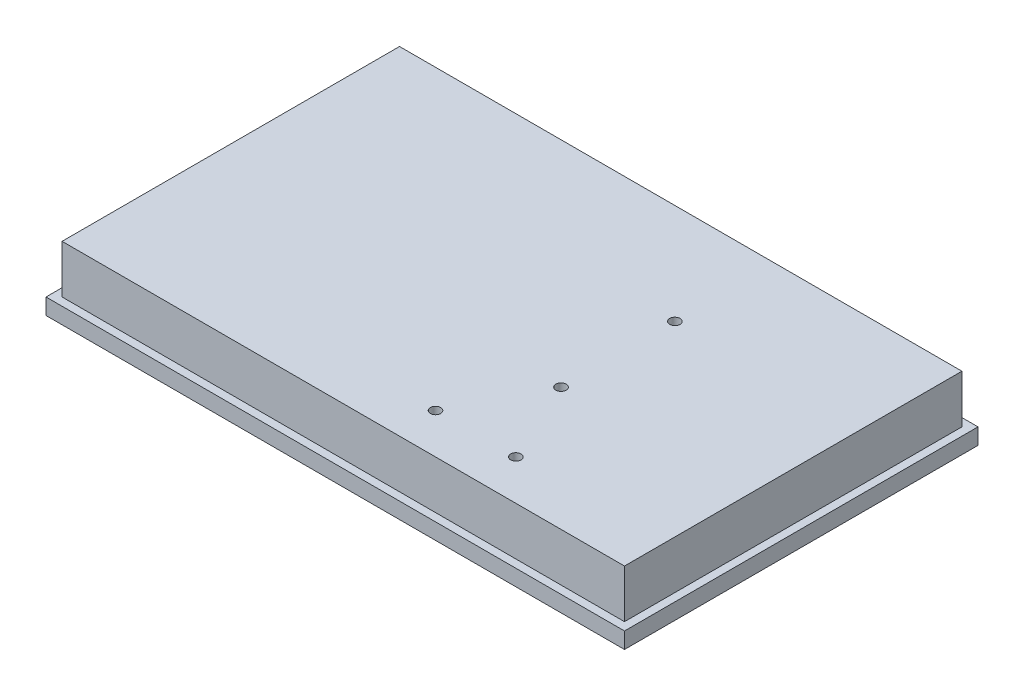
SolidWorks part; units mm, degrees
material "Gray Cast Iron"
ref_plane "Front Plane" through (0, 0, 0) normal (0, 0, 1) x (1, 0, 0)
ref_plane "Top Plane" through (0, 0, 0) normal (0, 1, 0) x (1, 0, 0)
ref_plane "Right Plane" through (0, 0, 0) normal (1, 0, 0) x (0, 0, -1)
sketch "Sketch1" plane through (0, 0, 0) normal (0, 1, 0) x (1, 0, 0)
  line L0 (-228.6, -139.7) -> (228.6, -139.7)
  line L1 (228.6, -139.7) -> (228.6, 139.7)
  line L2 (228.6, 139.7) -> (-228.6, 139.7)
  line L3 (-228.6, 139.7) -> (-228.6, -139.7)
  dimension "D1" = 457.2
  dimension "D2" = 279.4
  dimension "D3" = 228.6
  dimension "D4" = 139.7
extrude "Boss-Extrude1" add sketch "Sketch1" along normal blind 12.7
sketch "Sketch2" plane through (0, 0, 0) normal (0, 1, 0) x (1, 0, 0)
  line L0 (-222.25, -133.35) -> (222.25, -133.35)
  line L1 (222.25, -133.35) -> (222.25, 133.35)
  line L2 (222.25, 133.35) -> (-222.25, 133.35)
  line L3 (-222.25, 133.35) -> (-222.25, -133.35)
  dimension "D1" = 444.5
  dimension "D2" = 266.7
  dimension "D3" = 222.25
  dimension "D4" = 133.35
extrude "Boss-Extrude2" add sketch "Sketch2" along normal blind 38.1 from offset 12.7
sketch "Sketch3" plane through (0, 0, 0) normal (0, 1, 0) x (1, 0, 0)
  circle A0 centre (74.75, 54) radius 4.1
  circle A1 centre (74.75, -36) radius 4.1
  circle A2 centre (41.15, -101.6) radius 4.1
  circle A3 centre (104.65, -101.6) radius 4.1
  dimension "D3" = 8.2
  dimension "D6" = 8.2
  dimension "D9" = 8.2
  dimension "D12" = 8.2
  dimension "D1" = 74.75
  dimension "D2" = 54
  dimension "D4" = 74.75
  dimension "D5" = 36
  dimension "D7" = 41.15
  dimension "D8" = 101.6
  dimension "D10" = 104.65
  dimension "D11" = 101.6
extrude "Cut-Extrude1" cut sketch "Sketch3" against normal mid plane 152.4
sketch "Sketch4" plane through (0, 0, 0) normal (0, 1, 0) x (1, 0, 0)
  circle A0 centre (41.15, -101.6) radius 7.5
  circle A1 centre (104.65, -101.6) radius 7.5
  dimension "D3" = 15
  dimension "D6" = 15
  dimension "D1" = 41.15
  dimension "D2" = 101.6
  dimension "D4" = 104.65
  dimension "D5" = 101.6
extrude "Cut-Extrude2" cut sketch "Sketch4" against normal mid plane 9
